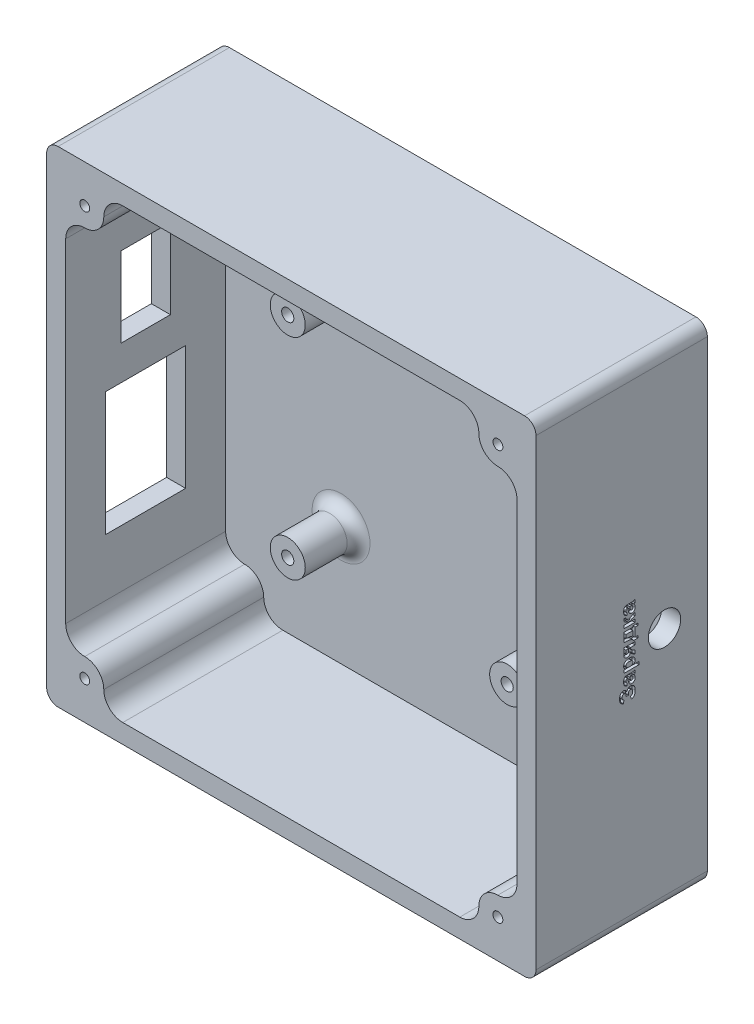
SolidWorks part; units mm, degrees
ref_plane "Спереди" through (0, 0, 0) normal (0, 0, 1) x (1, 0, 0)
ref_plane "Сверху" through (0, 0, 0) normal (0, 1, 0) x (1, 0, 0)
ref_plane "Справа" through (0, 0, 0) normal (1, 0, 0) x (0, 0, -1)
sketch "Эскиз1" plane through (0, 0, 0) normal (0, 0, 1) x (1, 0, 0)
  line L1 (-39.25, 38.75) -> (39.25, 38.75)
  line L2 (-39.25, 38.75) -> (-39.25, -38.75)
  line L3 (-39.25, -38.75) -> (39.25, -38.75)
  line L4 (39.25, 38.75) -> (39.25, -38.75)
  line L5 (-39.25, 38.75) -> (39.25, -38.75) construction
  line L6 (-39.25, -38.75) -> (39.25, 38.75) construction
  point P0 (0, 0)
  dimension "D1" = 78.5
  dimension "D2" = 77.5
extrude "Бобышка-Вытянуть1" add sketch "Эскиз1" along normal blind 3
sketch "Эскиз2" plane through (0, 0, 3) normal (0, 0, 1) x (1, 0, 0)
  line L0 (39.25, 38.75) -> (-39.25, 38.75) construction
  line L1 (-28.94, 35.4) -> (47.4553, 35.4) construction
  line L2 (-39.25, 38.75) -> (-39.25, -38.75) construction
  line L3 (-9.735, 38.75) -> (-9.735, 30.1091) construction
  line L4 (9.475, 38.75) -> (9.475, 29.1142) construction
  line L5 (28.685, 38.75) -> (28.685, 29.1142) construction
  line L6 (0, 0) -> (58.8259, 0) construction
  line L7 (0, 0) -> (-46.7985, 0) construction
  line L8 (-28.94, 35.4) -> (-28.94, -35.4) construction
  line L9 (-9.735, 35.4) -> (-9.735, -35.4) construction
  line L10 (9.475, 35.4) -> (9.475, -35.4) construction
  line L11 (28.685, 35.4) -> (28.685, -35.4) construction
  line L12 (-28.94, 27.6) -> (34.6216, 27.6) construction
  circle A8 centre (-28.94, 27.6) radius 1.6
  circle A11 centre (28.685, 27.6) radius 1.6
  circle A12 centre (28.685, -27.6) radius 1.6
  circle A13 centre (-28.94, -27.6) radius 1.6
  point P0 (-28.945, 38.75)
  point P1 (-28.94, 35.4)
  point P7 (-9.735, 38.75)
  point P8 (9.475, 38.75)
  point P9 (28.685, 38.75)
  point P10 (-28.94, 27.6)
  point P24 (9.475, 35.4)
  point P25 (28.685, 35.4)
  point P42 (-9.735, 27.6)
  point P43 (9.475, 27.6)
  point P44 (28.685, 27.6)
  dimension "D3" = 3.2
  dimension "D1" = 10.305
  dimension "D2" = 3.35
  dimension "D4" = 19.21
  dimension "D5" = 19.21
  dimension "D6" = 19.21
  dimension "D7" = 10.31
  dimension "D8" = 7.8
extrude "Вырез-Вытянуть2" cut sketch "Эскиз2" against normal blind 3
sketch "Эскиз3" plane through (0, 0, 3) normal (0, 0, 1) x (1, 0, 0)
  circle A0 centre (-28.94, -27.6) radius 1.6 construction
  circle A1 centre (28.685, -27.6) radius 1.6 construction
  circle A2 centre (28.685, 27.6) radius 1.6 construction
  circle A3 centre (-28.94, 27.6) radius 1.6 construction
  circle A4 centre (-28.94, -27.6) radius 1.6
  circle A5 centre (28.685, -27.6) radius 1.6
  circle A6 centre (28.685, 27.6) radius 1.6
  circle A7 centre (-28.94, 27.6) radius 1.6
extrude "Вытянуть-Тонкостенный1" add sketch "Эскиз3" along normal blind 14 thin thin type one direction wall 3
sketch "Эскиз4" plane through (-39.25, 0, 0) normal (-1, 0, 0) x (0, 0, 1)
  line L4 (0, 38.75) -> (0, -38.75)
  line L5 (0, -38.75) -> (3, -38.75)
  line L6 (3, -38.75) -> (3, 38.75)
  line L7 (3, 38.75) -> (0, 38.75)
  line L8 (0, 38.75) -> (0, -38.75)
  line L9 (0, -38.75) -> (3, -38.75)
  line L10 (3, -38.75) -> (3, 38.75)
  line L11 (3, 38.75) -> (0, 38.75)
  dimension "D1" = 0
extrude "Бобышка-Вытянуть2" add sketch "Эскиз4" along normal blind 20
sketch "Эскиз5" plane through (39.25, 0, 0) normal (1, 0, 0) x (0, 0, -1)
  line L4 (0, -38.75) -> (0, 38.75)
  line L5 (0, 38.75) -> (-3, 38.75)
  line L6 (-3, 38.75) -> (-3, -38.75)
  line L7 (-3, -38.75) -> (0, -38.75)
  line L8 (0, -38.75) -> (0, 38.75)
  line L9 (0, 38.75) -> (-3, 38.75)
  line L10 (-3, 38.75) -> (-3, -38.75)
  line L11 (-3, -38.75) -> (0, -38.75)
  dimension "D1" = 0
extrude "Бобышка-Вытянуть3" add sketch "Эскиз5" along normal blind 20
sketch "Эскиз6" plane through (0, 38.75, 0) normal (0, 1, 0) x (1, 0, 0)
  line L4 (59.25, 0) -> (-59.25, 0)
  line L5 (-59.25, 0) -> (-59.25, -3)
  line L6 (-59.25, -3) -> (59.25, -3)
  line L7 (59.25, -3) -> (59.25, 0)
  line L8 (59.25, 0) -> (-59.25, 0)
  line L9 (-59.25, 0) -> (-59.25, -3)
  line L10 (-59.25, -3) -> (59.25, -3)
  line L11 (59.25, -3) -> (59.25, 0)
  dimension "D1" = 0
extrude "Бобышка-Вытянуть4" add sketch "Эскиз6" along normal blind 20
sketch "Эскиз7" plane through (0, -38.75, 0) normal (0, -1, 0) x (1, 0, 0)
  line L4 (-59.25, 0) -> (59.25, 0)
  line L5 (59.25, 0) -> (59.25, 3)
  line L6 (59.25, 3) -> (-59.25, 3)
  line L7 (-59.25, 3) -> (-59.25, 0)
  line L8 (-59.25, 0) -> (59.25, 0)
  line L9 (59.25, 0) -> (59.25, 3)
  line L10 (59.25, 3) -> (-59.25, 3)
  line L11 (-59.25, 3) -> (-59.25, 0)
  dimension "D1" = 0
extrude "Бобышка-Вытянуть5" add sketch "Эскиз7" along normal blind 20
sketch "Эскиз8" plane through (0, 0, 3) normal (0, 0, 1) x (1, 0, 0)
  line L4 (-59.25, 58.75) -> (-59.25, -58.75)
  line L5 (-59.25, -58.75) -> (59.25, -58.75)
  line L6 (59.25, -58.75) -> (59.25, 58.75)
  line L7 (59.25, 58.75) -> (-59.25, 58.75)
  line L8 (-59.25, 58.75) -> (-59.25, -58.75)
  line L9 (-59.25, -58.75) -> (59.25, -58.75)
  line L10 (59.25, -58.75) -> (59.25, 58.75)
  line L11 (59.25, 58.75) -> (-59.25, 58.75)
  dimension "D1" = 0
extrude "Вытянуть-Тонкостенный2" add sketch "Эскиз8" along normal blind 42 and the other way blind 3 thin thin type one direction wall 5
sketch "Эскиз9" plane through (0, 0, 3) normal (0, 0, 1) x (1, 0, 0)
  line L2 (59.25, 58.75) -> (-59.25, 58.75) construction
  line L3 (-59.25, -58.75) -> (-59.25, 58.75) construction
  line L6 (-49.25, 58.75) -> (-59.25, 58.75)
  line L7 (-59.25, 48.75) -> (-59.25, 58.75)
  line L8 (0, 0) -> (0, -78.0698) construction
  line L9 (-59.25, 58.75) -> (-49.25, 58.75)
  line L10 (-59.25, 58.75) -> (-59.25, 48.75)
  line L11 (-59.25, 48.75) -> (-49.25, 48.75)
  line L12 (-49.25, 58.75) -> (-49.25, 48.75)
  line L13 (0, 0) -> (96.8588, 0) construction
  line L14 (-59.25, -48.75) -> (-49.25, -48.75)
  line L15 (-49.25, -58.75) -> (-49.25, -48.75)
  line L16 (-59.25, -58.75) -> (-49.25, -58.75)
  line L17 (-59.25, -58.75) -> (-59.25, -48.75)
  line L18 (59.25, -58.75) -> (59.25, -48.75)
  line L19 (59.25, -58.75) -> (49.25, -58.75)
  line L20 (49.25, -58.75) -> (49.25, -48.75)
  line L21 (59.25, -48.75) -> (49.25, -48.75)
  line L22 (59.25, 48.75) -> (49.25, 48.75)
  line L23 (49.25, 58.75) -> (49.25, 48.75)
  line L24 (59.25, 58.75) -> (49.25, 58.75)
  line L25 (59.25, 58.75) -> (59.25, 48.75)
  line M16 (-59.25, 58.75) -> (-59.25, -58.75)
  line M17 (-59.25, -58.75) -> (59.25, -58.75)
  line M18 (59.25, -58.75) -> (59.25, 58.75)
  line M19 (59.25, 58.75) -> (-59.25, 58.75)
  dimension "D1" = 10
  dimension "D2" = 10
extrude "Бобышка-Вытянуть6" add sketch "Эскиз9" along normal blind 42 contours L21 L20 M18 M17 | L15 L14 M17 M16 | L12 L11 M19 M16 | L23 L22 M19 M18 region at (-54.25, 53.75, 3) region at (54.25, 53.75, 3) region at (-54.25, -53.75, 3) region at (54.25, -53.75, 3)
sketch "Эскиз10" plane through (0, 0, 45) normal (0, 0, 1) x (1, 0, 0)
  line L0 (-49.25, 58.75) -> (-59.25, 48.75) construction
  line L1 (0, 0) -> (0, -67.5444) construction
  line L2 (0, 0) -> (70.0236, 0) construction
  line L3 (-59.25, 58.75) -> (-49.25, 48.75) construction
  circle A0 centre (-54.25, 53.75) radius 1.3
  circle A1 centre (-54.25, -53.75) radius 1.3
  circle A2 centre (54.25, 53.75) radius 1.3
  circle A3 centre (54.25, -53.75) radius 1.3
  point P7 (-59.25, 58.75)
  point P12 (-54.25, 53.75)
  dimension "D3" = 2.6
  dimension "D1" = 10
  dimension "D2" = 10
extrude "Вырез-Вытянуть3" cut sketch "Эскиз10" against normal blind 51
sketch "Эскиз11" plane through (0, 0, 0) normal (0, 0, -1) x (-1, 0, 0)
  line L0 (-28.685, 27.6) -> (28.94, 27.6) construction
  line L1 (-28.685, -27.6) -> (28.94, -27.6) construction
  line L3 (-25.5096, 27.6) -> (-27.0973, 30.35)
  line L4 (-27.0973, 30.35) -> (-30.2727, 30.35)
  line L5 (-30.2727, 30.35) -> (-31.8604, 27.6)
  line L6 (-31.8604, 27.6) -> (-30.2727, 24.85)
  line L7 (-30.2727, 24.85) -> (-27.0973, 24.85)
  line L8 (-27.0973, 24.85) -> (-25.5096, 27.6)
  line L9 (25.7646, 27.6) -> (27.3523, 24.85)
  line L10 (27.3523, 24.85) -> (30.5277, 24.85)
  line L11 (30.5277, 24.85) -> (32.1154, 27.6)
  line L12 (32.1154, 27.6) -> (30.5277, 30.35)
  line L13 (30.5277, 30.35) -> (27.3523, 30.35)
  line L14 (27.3523, 30.35) -> (25.7646, 27.6)
  line L15 (-25.5096, -27.6) -> (-27.0973, -24.85)
  line L16 (-27.0973, -24.85) -> (-30.2727, -24.85)
  line L17 (-30.2727, -24.85) -> (-31.8604, -27.6)
  line L18 (-31.8604, -27.6) -> (-30.2727, -30.35)
  line L19 (-30.2727, -30.35) -> (-27.0973, -30.35)
  line L20 (-27.0973, -30.35) -> (-25.5096, -27.6)
  line L21 (25.7646, -27.6) -> (27.3523, -30.35)
  line L22 (27.3523, -30.35) -> (30.5277, -30.35)
  line L23 (30.5277, -30.35) -> (32.1154, -27.6)
  line L24 (32.1154, -27.6) -> (30.5277, -24.85)
  line L25 (30.5277, -24.85) -> (27.3523, -24.85)
  line L26 (27.3523, -24.85) -> (25.7646, -27.6)
  circle A0 centre (-28.685, 27.6) radius 2.75 construction
  circle A1 centre (28.94, 27.6) radius 2.75 construction
  circle A2 centre (-28.685, -27.6) radius 2.75 construction
  circle A3 centre (28.94, -27.6) radius 2.75 construction
  dimension "D1" = 5.5
  dimension "D2" = 5.5
  dimension "D3" = 5.5
  dimension "D4" = 5.5
extrude "Вырез-Вытянуть4" cut sketch "Эскиз11" against normal blind 3
fillet "Скругление1" radius 5 12 edges at (-59.25, -48.75, 24) (-49.25, -48.75, 24) (-49.25, -58.75, 24) (49.25, -58.75, 24) (49.25, -48.75, 24) (59.25, -48.75, 24) (59.25, 48.75, 24) (49.25, 48.75, 24) (49.25, 58.75, 24) (-49.25, 48.75, 24) (-59.25, 48.75, 24) (-49.25, 58.75, 24)
fillet "Скругление3" radius 3 4 edges at (-64.25, 63.75, 22.5) (64.25, 63.75, 22.5) (64.25, -63.75, 22.5) (-64.25, -63.75, 22.5)
sketch "Эскиз12" plane through (64.25, 0, 0) normal (1, 0, 0) x (0, 0, -1)
  line L0 (0, 0) -> (-71.8029, 0) construction
  line L2 (-3, 43.75) -> (-3, -43.75) construction
  circle A0 centre (-11.25, 0) radius 4.25
  point P3 (-3, 0)
  point P5 (-7, 0)
  point P6 (-11.25, 0)
  dimension "D1" = 4
  dimension "D2" = 4.25
extrude "Вырез-Вытянуть5" cut sketch "Эскиз12" against normal blind 10
sketch "Эскиз13" plane through (64.25, 0, 0) normal (1, 0, 0) x (0, 0, -1)
  line L0 (-19, 43.6701) -> (-19, -43.4278) construction
  line L1 (0, -60.75) -> (0, 60.75) construction
  text T0 "<b>Зарядка</b>"
  dimension "D1" = 19
extrude "Вырез-Вытянуть6" cut sketch "Эскиз13" against normal blind 0.8
sketch "Эскиз14" plane through (-64.25, 0, 0) normal (-1, 0, 0) x (0, 0, 1)
  line L0 (24, 43.75) -> (24, -43.75) construction
  line L1 (17.5, 33.75) -> (30.5, 33.75)
  line L2 (30.5, 33.75) -> (30.5, 12.75)
  line L3 (30.5, 12.75) -> (17.5, 12.75)
  line L12 (17.5, 33.75) -> (17.5, 12.75)
  line L13 (34.5, -28.75) -> (13.5, -28.75)
  line L14 (0, 60.75) -> (0, -60.75) construction
  line L15 (13.5, -28.75) -> (13.5, 3.75)
  line L16 (13.5, 3.75) -> (34.5, 3.75)
  line L17 (34.5, -28.75) -> (34.5, 3.75)
  point P6 (24, 33.75)
  point P11 (24, -28.75)
  point P12 (24, 33.75)
  point P13 (24, 12.75)
  point P21 (24, -28.75)
  point P22 (24, 3.75)
  dimension "D2" = 10
  dimension "D3" = 6.5
  dimension "D4" = 21
  dimension "D5" = 15
  dimension "D6" = 10.5
  dimension "D7" = 32.5
extrude "Вырез-Вытянуть7" cut sketch "Эскиз14" against normal blind 10
sketch "Эскиз15" plane through (-64.25, 0, 0) normal (-1, 0, 0) x (0, 0, 1)
  line L0 (5.0419, 60.75) -> (5.0419, -60.75) construction
  line L1 (45, 60.75) -> (0, 60.75) construction
  line L2 (0, -60.75) -> (45, -60.75) construction
  text T0 "<b>                Вкл/Выкл   Уровень заряда</b>"
extrude "Вырез-Вытянуть8" cut sketch "Эскиз15" against normal blind 0.8
fillet "Скругление5" radius 3 4 edges at (33.285, -27.6, 3) (-24.34, -27.6, 3) (33.285, 27.6, 3) (-24.34, 27.6, 3)
